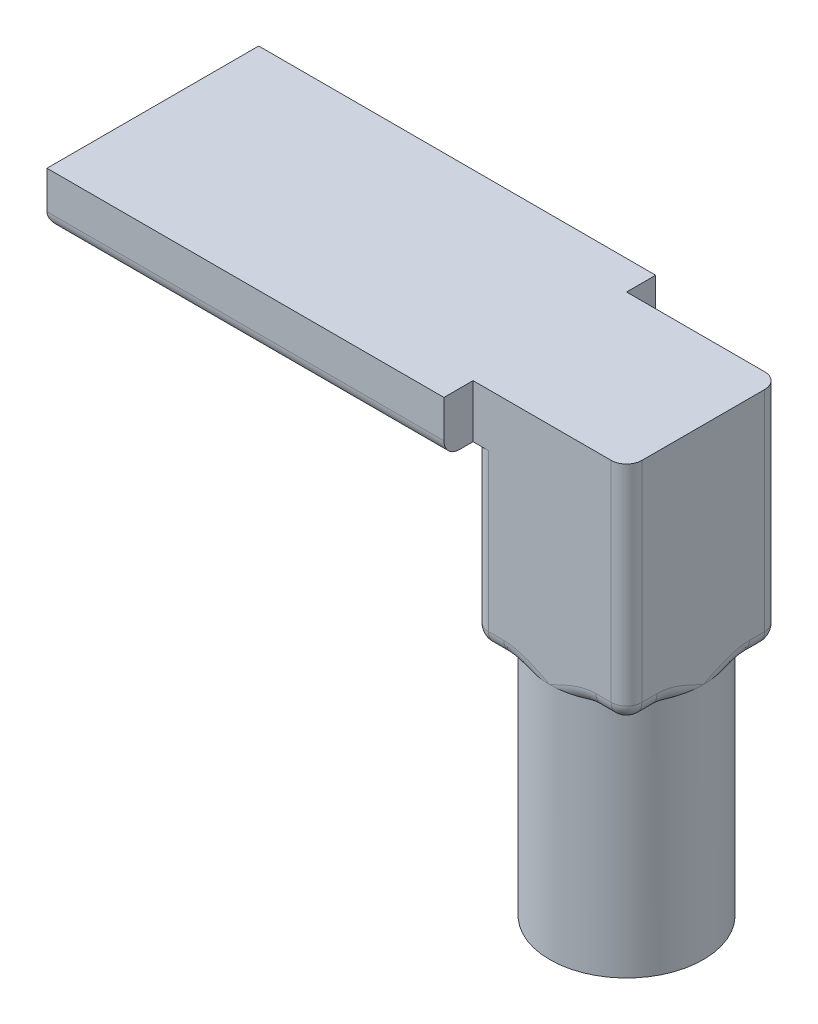
SolidWorks part; units mm, degrees
ref_plane "Front Plane" through (0, 0, 0) normal (0, 0, 1) x (1, 0, 0)
ref_plane "Top Plane" through (0, 0, 0) normal (0, 1, 0) x (1, 0, 0)
ref_plane "Right Plane" through (0, 0, 0) normal (1, 0, 0) x (0, 0, -1)
sketch "Sketch1" plane through (0, 0, 0) normal (0, 1, 0) x (1, 0, 0)
  circle A0 centre (0, 0) radius 2.9
  point P3 (-155.2684, 5.1331)
extrude "Boss-Extrude1" add sketch "Sketch1" along normal blind 9
sketch "Sketch2" plane through (0, 9, 0) normal (0, 1, 0) x (1, 0, 0)
  line L0 (0, 2.9) -> (-4.8229, 2.9)
  line L1 (0, 2.9) -> (4.9125, 2.9)
  line L2 (2.9, 0) -> (2.9, 2.9)
  line L3 (2.9, 0) -> (2.9, -5.2233)
  line L4 (0, -2.9) -> (2.9, -2.9)
  line L5 (0, -2.9) -> (-8.5076, -2.9)
  line L6 (-2.9, 0) -> (-2.9, -2.9)
  line L7 (-2.9, 0) -> (-2.9, 2.9)
  line L8 (-2.9, -2.9) -> (2.9, -2.9)
  line L9 (2.9, 2.9) -> (-2.9, 2.9)
  circle A0 centre (0, 0) radius 2.9 construction
  circle M1 centre (0, 0) radius 2.9
extrude "Boss-Extrude2" add sketch "Sketch2" along normal blind 8.5 contours M1 | L6 L5 M1 | L7 L0 M1 | L2 L1 M1 | L4 L3 M1 region at (-2.2522, 9, -2.2522) region at (2.2522, 9, -2.2522) region at (0, 9, 0) region at (2.2522, 9, 2.2522) region at (-2.2522, 9, 2.2522)
sketch "Sketch3" plane through (-2.9, 0, 0) normal (-1, 0, 0) x (0, 0, 1)
  line L0 (2.9, 17.5) -> (2.9, 9) construction
  line L1 (-2.9, 17.5) -> (2.9, 17.5)
  line L2 (-2.9, 17.5) -> (-2.9, 15.5)
  line L3 (-2.9, 15.5) -> (2.9, 15.5)
  line L4 (2.9, 17.5) -> (2.9, 15.5)
extrude "Boss-Extrude3" add sketch "Sketch3" along normal blind 10
sketch "Sketch4" plane through (-12.9, 0, 0) normal (-1, 0, 0) x (0, 0, 1)
  line L1 (-2.9, 17.5) -> (2.9, 17.5)
  line L2 (-2.9, 17.5) -> (-2.9, 15.5)
  line L3 (-2.9, 15.5) -> (2.9, 15.5)
  line L4 (2.9, 17.5) -> (2.9, 15.5)
extrude "Boss-Extrude4" add sketch "Sketch4" along normal blind 5
sketch "Sketch5" plane through (0, 17.5, 0) normal (0, 1, 0) x (1, 0, 0)
  line L0 (-17.9, 2.9) -> (-17.9, -2.9)
sketch "Sketch6" plane through (0, 0, 2.9) normal (0, 0, 1) x (1, 0, 0)
  line L1 (-17.9, 17.5) -> (-2.9, 17.5)
  line L2 (-17.9, 17.5) -> (-17.9, 15.5)
  line L3 (-17.9, 15.5) -> (-2.9, 15.5)
  line L4 (-2.9, 17.5) -> (-2.9, 15.5)
extrude "Boss-Extrude5" add sketch "Sketch6" along normal blind 1.1
sketch "Sketch7" plane through (0, 0, -2.9) normal (0, 0, -1) x (-1, 0, 0)
  line L1 (2.9, 15.5) -> (17.9, 15.5)
  line L2 (2.9, 15.5) -> (2.9, 17.5)
  line L3 (2.9, 17.5) -> (17.9, 17.5)
  line L4 (17.9, 15.5) -> (17.9, 17.5)
extrude "Boss-Extrude6" add sketch "Sketch7" along normal blind 1.1
fillet "Fillet1" radius 0.58 15 edges at (-2.9, 9, -1.45) (-1.45, 9, 2.9) (2.9, 9, -1.45) (-1.45, 9, -2.9) (-2.9, 9, 1.45) (1.45, 9, 2.9) (2.9, 9, 1.45) (1.45, 9, -2.9) (-17.9, 15.5, 0) (-10.4, 15.5, 4) (-10.4, 15.5, -4) (-2.9, 12.25, -2.9) (2.9, 13.25, -2.9) (2.9, 13.25, 2.9) (-2.9, 12.25, 2.9)
